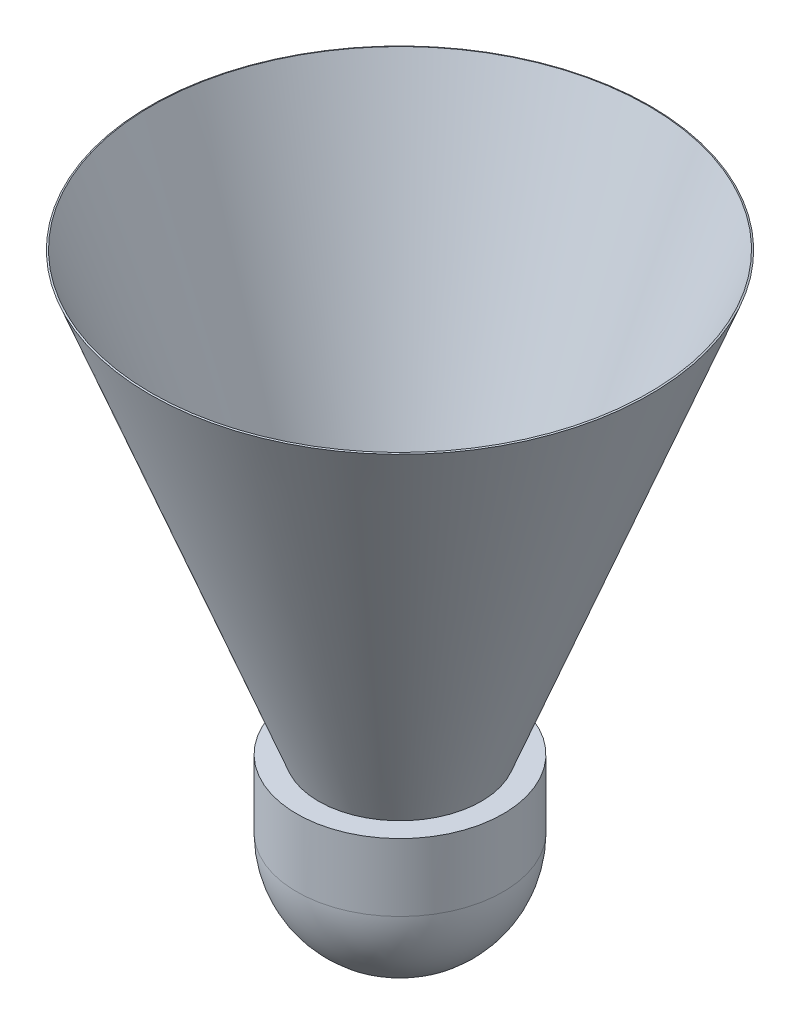
SolidWorks part; units mm, degrees
ref_plane "Front Plane" through (0, 0, 0) normal (0, 0, 1) x (1, 0, 0)
ref_plane "Top Plane" through (0, 0, 0) normal (0, 1, 0) x (1, 0, 0)
ref_plane "Right Plane" through (0, 0, 0) normal (1, 0, 0) x (0, 0, -1)
sketch "Sketch1" plane through (0, 0, 0) normal (0, 0, 1) x (1, 0, 0)
  line L0 (13, 8.5) -> (10.25, 8.5)
  line L1 (13, 0) -> (13, 8.5)
  line L2 (0, -13) -> (0, 8.5) construction
  line L3 (10.25, 8.5) -> (31.5, 63.5)
  line L4 (31.5, 63.5) -> (31.3134, 63.5721)
  line L5 (31.3134, 63.5721) -> (10.0356, 8.5)
  line L6 (10.0356, 8.5) -> (0, 8.5)
  line L7 (0, 8.5) -> (0, -13)
  arc A0 (0, -13) -> (13, 0) centre (0, 0) ccw
  dimension "D1" = 26
  dimension "D2" = 21.5
  dimension "D3" = 10.25
  dimension "D4" = 55
  dimension "D5" = 31.5
  dimension "D6" = 0.2
revolve "Revolve1" add sketch "Sketch1" angle 360 about L2
